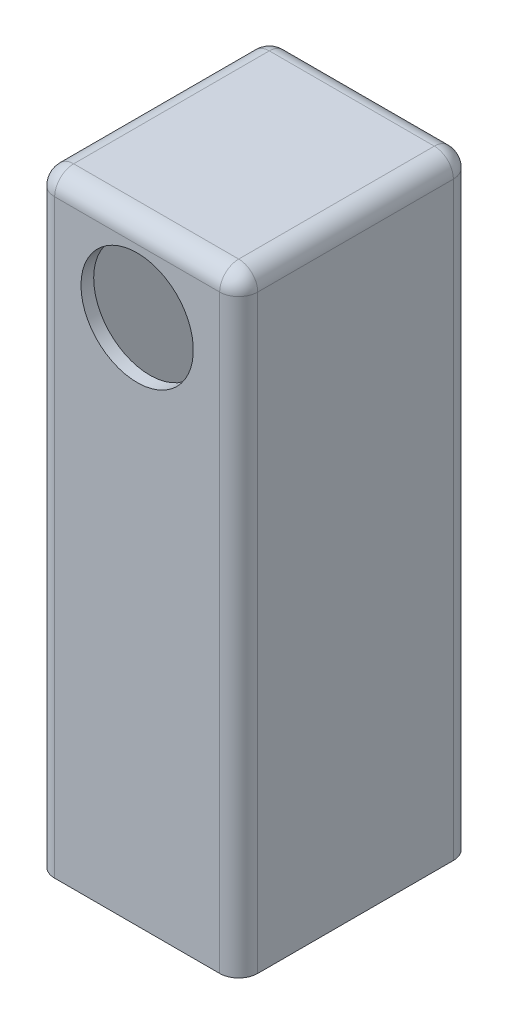
SolidWorks part; units mm, degrees
ref_plane "Front Plane" through (0, 0, 0) normal (0, 0, 1) x (1, 0, 0)
ref_plane "Top Plane" through (0, 0, 0) normal (0, 1, 0) x (1, 0, 0)
ref_plane "Right Plane" through (0, 0, 0) normal (1, 0, 0) x (0, 0, -1)
sketch "Print limits" plane through (0, 0, 0) normal (0, 1, 0) x (1, 0, 0)
  line L1 (70, 70) -> (-70, 70)
  line L2 (70, 70) -> (70, -70)
  line L3 (70, -70) -> (-70, -70)
  line L4 (-70, 70) -> (-70, -70)
  line L5 (0, -70) -> (0, 70) construction
  line L6 (70, 0) -> (-70, 0) construction
  line L7 (85, 85) -> (-85, 85)
  line L8 (85, 85) -> (85, -85)
  line L9 (85, -85) -> (-85, -85)
  line L10 (-85, 85) -> (-85, -85)
  line L11 (0, -85) -> (0, 85) construction
  line L12 (85, 0) -> (-85, 0) construction
  point P0 (0, 0)
  point P4 (0, 0)
  dimension "D1" = 170
  dimension "D2" = 140
sketch "Sketch2" plane through (0, 0, 0) normal (0, 1, 0) x (1, 0, 0)
  line L2 (70, -70) -> (-70, -70) construction
  line L4 (70, 70) -> (70, -70) construction
  line L8 (-70, 70) -> (-70, -70) construction
  line L9 (70, -70) -> (-70, -70)
  line L10 (70, 94.0926) -> (70, -70)
  line L11 (70, 94.0926) -> (-70, 94.0926)
  line L12 (-70, 94.0926) -> (-70, -70)
extrude "Boss-Extrude1" add sketch "Sketch2" against normal blind 469.9
shell "Shell1" thickness 10 removed face at (0, -469.9, -12.0463) outward yes
fillet "Fillet2" radius 15 8 edges at (0, 10, 80) (-80, 10, -12.0463) (0, 10, -104.0926) (80, 10, -12.0463) (80, -229.95, -104.0926) (-80, -229.95, -104.0926) (-80, -229.95, 80) (80, -229.95, 80)
sketch "Sketch4" plane through (44.6751, 0, 80) normal (0, 0, -1) x (-1, 0, 0)
  line L0 (44.6751, -55) -> (44.6751, 0) construction
  line L2 (-20.3249, 10) -> (109.6751, 10) construction
  circle A0 centre (44.6751, -55) radius 44.25
  dimension "D1" = 88.5
  dimension "D2" = 65
extrude "Cut-Extrude2" cut sketch "Sketch4" along normal blind 10
